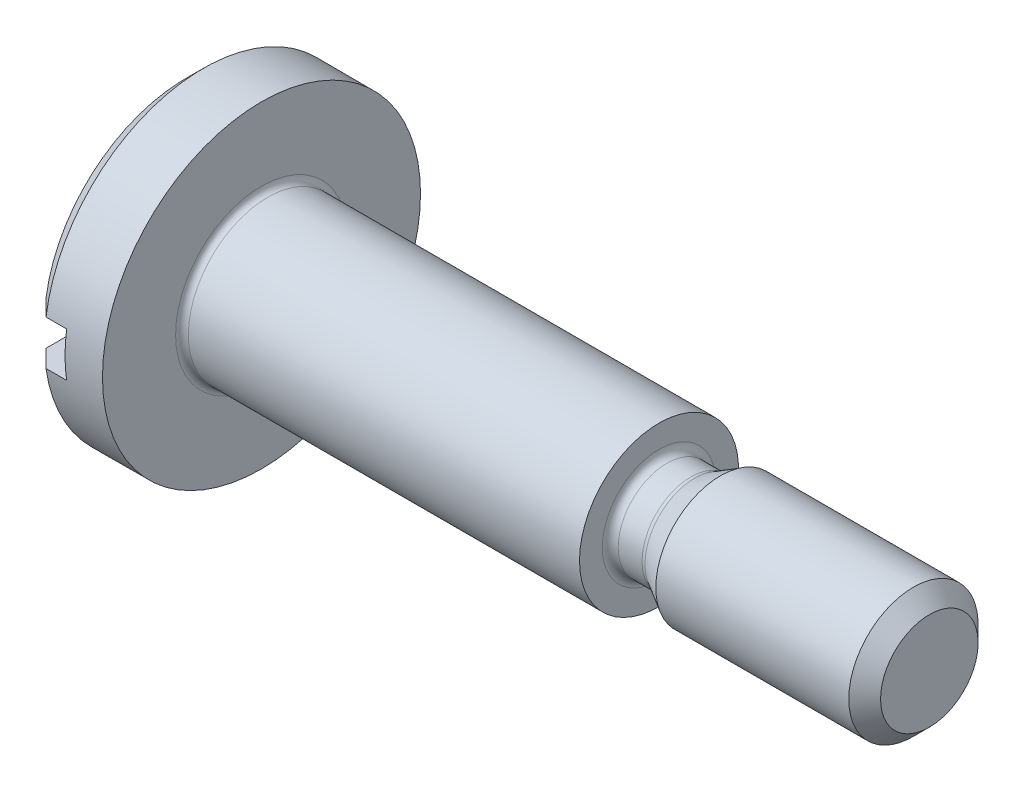
SolidWorks part; units mm, degrees
revolve "Base-Revolve" add sketch "BodySke" angle 360 about L2 other way angle 60
sketch "BodySke" plane through (0, 0, 0) normal (0, 0, 1) x (1, 0, 0)
  line L0 (4.75, 5) -> (4.75, 10)
  line L1 (0, 0) -> (0, 8.9)
  line L2 (-25.4, 0) -> (127, 0) construction
  line L3 (46.75, 0) -> (0, 0)
  line L4 (4.75, 5) -> (29.75, 5)
  line L5 (46.75, 3.0663) -> (46.75, 0)
  line L6 (1.1, 10) -> (4.75, 10)
  line L7 (45.75, 4.0663) -> (33.616, 4.0663)
  line L8 (1.1, 10) -> (0, 8.9)
  line L9 (6, 6.5875) -> (6, -2.9375) construction
  line L11 (29.75, 5) -> (29.75, 3.5663)
  line L12 (30.25, 3.0663) -> (31.75, 3.0663)
  line L13 (32, 3.1333) -> (33.616, 4.0663)
  line L14 (46.75, 3.0663) -> (45.75, 4.0663)
  arc A0 (30.25, 3.0663) -> (29.75, 3.5663) centre (30.25, 3.5663) cw
  arc A1 (32, 3.1333) -> (31.75, 3.0663) centre (31.75, 3.5663) cw
  point P6 (46.75, 4.0663)
  dimension "Length" = 25
  dimension "Head_ht" = 4.75
  dimension "Head_dia" = 20
  dimension "Diameter" = 10
  dimension "D1" = 45
  dimension "Neck" = 2
cosmetic thread "ThreadCosmetic" [suppressed] parameters "Thread_minor"=6.1325
ref_plane "Plane1" through (0, 0, 0) normal (0, 0, 1) x (1, 0, 0)
ref_plane "Plane2" through (0, 0, 0) normal (0, 1, 0) x (1, 0, 0)
ref_plane "Plane3" through (0, 0, 0) normal (1, 0, 0) x (0, 0, -1)
fillet "Fillet1" radius 0.4 1 edges at (4.75, 0, 5)
sketch "Sketch2" plane through (0, 0, 0) normal (1, 0, 0) x (0, 0, -1)
  line L0 (10, -1.4) -> (-10, -1.4)
  line L1 (10, -1.4) -> (10, 1.4)
  line L2 (-10, 1.4) -> (10, 1.4)
  line L3 (-10, 1.4) -> (-10, -1.4)
  line L4 (10, 1.4) -> (-10, -1.4) construction
  dimension "D1" = 20
extrude "Slot" cut sketch "Sketch2" along normal blind 2.4
sketch "ThdSchSke" plane through (0, 0, 0) normal (0, 0, 1) x (1, 0, 0)
  line L0 (33, -3.0663) -> (31.646, -5)
  line L1 (33, -3.0663) -> (34.354, -5)
  line L2 (34.354, -5) -> (34.354, -6.25)
  line L3 (-3.175, 0) -> (5.1513, 0) construction
  line L5 (34.354, -6.25) -> (31.646, -6.25)
  line L6 (31.646, -6.25) -> (31.646, -5)
  line L7 (46.75, -5) -> (46.75, 5) construction
  dimension "Diameter" = 10
  dimension "Thread_minor" = 6.1325
  dimension "Start" = 13.75
revolve "ThreadSchematic" [suppressed] cut sketch "ThdSchSke" angle 360 about L3
pattern_linear "ThdSchPat" [suppressed]
equation "\"D1@Sketch2\" = \"Head_dia@BodySke\""
equation "\"Thread_minor@ThreadCosmetic\" = \"Minor_dia@BodySke\""
equation "\"Thread_minor@ThdSchSke\" = \"Minor_dia@BodySke\""
equation "\"Diameter@ThdSchSke\" = \"Diameter@BodySke\""
equation "\"Overcut@ThdSchSke\" = \"Diameter@BodySke\" * 1.25"
equation "\"Start@ThdSchSke\" = \"Thread_nom@BodySke\" - \"Neck@BodySke\" - \"Advance@BodySke\""
equation "\"Num_threads@ThdSchPat\" = int( \"Start@ThdSchSke\" / \"Advance@BodySke\" + 0.999 )  + 1"
equation "\"Advance@ThdSchPat\" = \"Start@ThdSchSke\" /  (\"Num_threads@ThdSchPat\" - 1) 'relax it"
